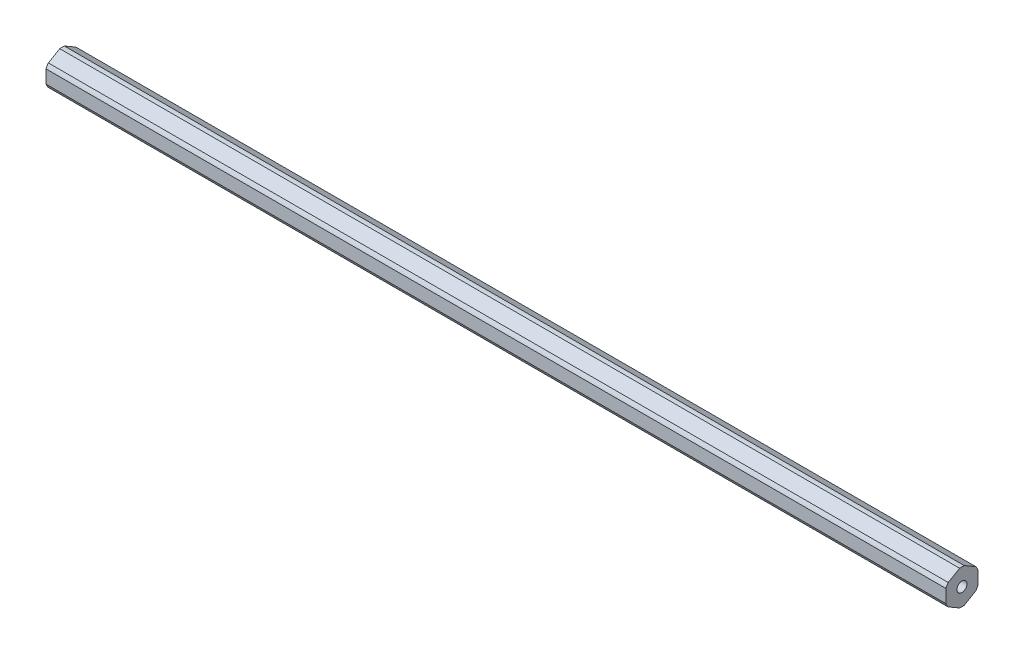
SolidWorks part; units mm, degrees
material "6061 Alloy"
ref_plane "Front Plane" through (0, 0, 0) normal (0, 0, 1) x (1, 0, 0)
ref_plane "Top Plane" through (0, 0, 0) normal (0, 1, 0) x (1, 0, 0)
ref_plane "Right Plane" through (0, 0, 0) normal (1, 0, 0) x (0, 0, -1)
ref_plane "Plane1" through (914.4, 0, 0) normal (1, 0, 0) x (0, 0, -1)
sketch "Sketch1" plane through (914.4, 0, 0) normal (1, 0, 0) x (0, 0, -1)
  line L0 (-5.4343, -4.1949) -> (-0.9157, -6.8037)
  line L1 (0.9157, -6.8037) -> (5.4343, -4.1949)
  line L2 (6.35, -2.6088) -> (6.35, 2.6088)
  line L3 (5.4343, 4.1949) -> (0.9157, 6.8037)
  line L4 (-0.9157, 6.8037) -> (-5.4343, 4.1949)
  line L5 (-6.35, 2.6088) -> (-6.35, -2.6088)
  circle A0 centre (0, 0) radius 1.9939
  arc A1 (-6.35, -2.6088) -> (-5.4343, -4.1949) centre (0, 0) ccw
  arc A2 (-0.9157, -6.8037) -> (0.9157, -6.8037) centre (0, 0) ccw
  arc A3 (5.4343, -4.1949) -> (6.35, -2.6088) centre (0, 0) ccw
  arc A4 (6.35, 2.6088) -> (5.4343, 4.1949) centre (0, 0) ccw
  arc A5 (0.9157, 6.8037) -> (-0.9157, 6.8037) centre (0, 0) ccw
  arc A6 (-5.4343, 4.1949) -> (-6.35, 2.6088) centre (0, 0) ccw
extrude "Boss-Extrude1" add sketch "Sketch1" against normal mid plane 355.6
equation "\"Hex Length\"= 14"
equation "\"D1@Boss-Extrude1\"=\"Hex Length\""
